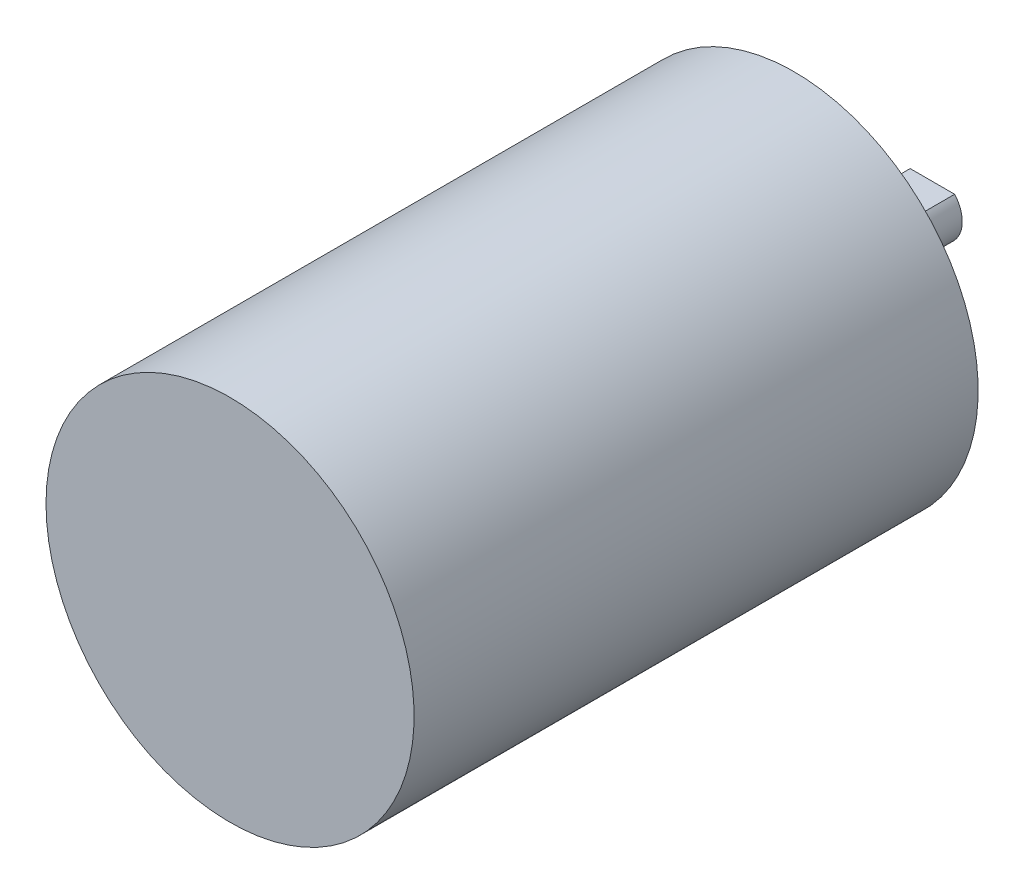
SolidWorks part; units mm, degrees
ref_plane "Front Plane" through (0, 0, 0) normal (0, 0, 1) x (1, 0, 0)
ref_plane "Top Plane" through (0, 0, 0) normal (0, 1, 0) x (1, 0, 0)
ref_plane "Right Plane" through (0, 0, 0) normal (1, 0, 0) x (0, 0, -1)
sketch "Sketch1" plane through (0, 0, 0) normal (0, 0, 1) x (1, 0, 0)
  circle A0 centre (0, 0) radius 18.5
  dimension "D1" = 37
extrude "Boss-Extrude1" add sketch "Sketch1" along normal blind 56.7
sketch "Sketch2" plane through (0, 0, 56.7) normal (0, 0, 1) x (1, 0, 0)
  point P0 (0, 0)
sketch "Sketch3" plane through (0, 0, 0) normal (0, 0, 1) x (1, 0, 0)
  circle A0 centre (0, 0) radius 6
  dimension "D1" = 12
extrude "Boss-Extrude2" add sketch "Sketch3" against normal blind 3.5
sketch "Sketch4" plane through (0, 0, -3.5) normal (0, 0, -1) x (-1, 0, 0)
  circle A0 centre (0, 0) radius 3
  dimension "D1" = 6
extrude "Boss-Extrude3" add sketch "Sketch4" along normal blind 10.4
sketch "Sketch5" plane through (0, 0, -13.9) normal (0, 0, -1) x (-1, 0, 0)
  line L0 (-2.2361, 2) -> (2.2361, 2)
  line L1 (0, 2) -> (0, 3) construction
  circle A0 centre (0, 0) radius 3 construction
  arc A1 (2.2361, 2) -> (-2.2361, 2) centre (0, 0) ccw
  dimension "D1" = 1
extrude "Cut-Extrude1" cut sketch "Sketch5" against normal blind 8
equation "\"MotorDIA\"= 37'ME 405 Motor Diameter"
equation "\"SyringeDIA\"= 31.4'60ml Syringe Diameter"
equation "\"MotorShaftDIA\"= 6'Motor Shaft Dia"
equation "\"MotorKeyway\"= 1'ME 405 Motor Shaft Keyway Depth"
equation "\"MotorLength\"= 56.7'ME 405 Motor Length Excluding Shaft"
equation "\"SyringeLength\"= 117.3'60ml Syringe Length Excluding Nozzle"
equation "\"3Dtol\"= .5'Sizing Tolerance for 3D printed parts"
equation "\"ChamberDIA\"= 100 - 4'Buoyancy Chamber inner Diameter"
equation "\"ChamberThk\"= 2mm'Buoyancy Chamber Wall Thickness"
equation "\"BearingOD\"= 10"
equation "\"BearingID\"= 4"
equation "\"Bearingwidth\"= 4"
equation "\"ShaftDIA\"= 4"
equation "\"D1@Sketch1\"=\"MotorDIA\""
equation "\"D1@Boss-Extrude1\"=\"MotorLength\""
